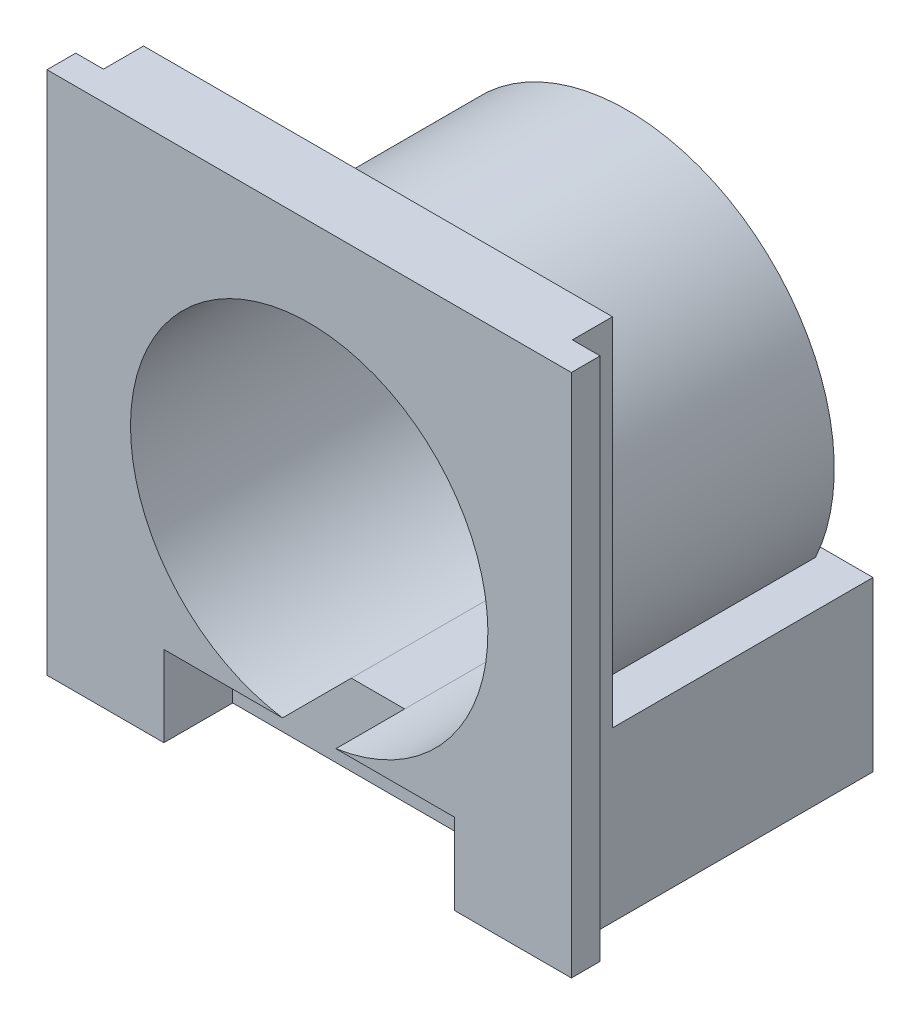
SolidWorks part; units mm, degrees
ref_plane "Front Plane" through (0, 0, 0) normal (0, 0, 1) x (1, 0, 0)
ref_plane "Top Plane" through (0, 0, 0) normal (0, 1, 0) x (1, 0, 0)
ref_plane "Right Plane" through (0, 0, 0) normal (1, 0, 0) x (0, 0, -1)
sketch "Sketch1" plane through (0, 0, 0) normal (0, 1, 0) x (1, 0, 0)
  line L0 (5.0691, -1.5049) -> (-12.7617, -1.505)
  line L1 (-12.7617, 8.401) -> (5.0691, 8.401)
  line L2 (-12.7617, 8.401) -> (-12.7617, -4.1212)
  line L3 (-12.7617, -4.1212) -> (5.0691, -4.1212)
  line L4 (5.0691, 8.401) -> (5.0691, -4.1212)
  line L5 (-13.8158, -3.029) -> (6.1232, -3.029)
  line L6 (-13.8158, -3.029) -> (-13.8158, -4.1212)
  line L7 (-13.8158, -4.1212) -> (6.1232, -4.1212)
  line L8 (6.1232, -3.029) -> (6.1232, -4.1212)
  line L9 (-9.3708, -4.1212) -> (1.6782, -4.1212)
  line L10 (-9.3708, -4.1212) -> (-9.3708, -1.0224)
  line L11 (-9.3708, -1.0224) -> (1.6782, -1.0224)
  line L12 (1.6782, -4.1212) -> (1.6782, -1.0224)
  line L14 (-12.7617, -3.0289) -> (5.0691, -3.0289)
  line L15 (-12.7617, -3.0289) -> (-12.7617, -1.505)
  line L16 (-12.7617, -1.505) -> (5.0691, -1.5049)
  line L17 (5.0691, -3.0289) -> (5.0691, -1.5049)
  point P12 (-3.8463, -1.0224)
  point P13 (-3.8463, -4.1212)
  point P14 (-3.8463, -3.029)
  point P17 (-12.7617, -3.0289)
  point P18 (5.0691, -3.0289)
  dimension "D1" = 17.8308
  dimension "D2" = 12.5222
  dimension "D3" = 0
  dimension "D4" = 3.0988
  dimension "D5" = 11.049
  dimension "D6" = 0
  dimension "D7" = 1.0922
  dimension "D8" = 19.939
  dimension "D9" = 0
  dimension "D10" = 1.524
extrude "Boss-Extrude1" add sketch "Sketch1" along normal blind 6.4008 contours L12 L5 L4 L1 L2 L10 L11 | L10 L9 L12 L11 region at (-3.8463, 0, -3.5947)
extrude "Boss-Extrude2" add sketch "Sketch1<3>" along normal blind 19.939 contours L6 L7 L2 L5 | L3 L10 L5 L2 | L7 L12 L5 L10 | L12 L3 L4 L5 | L8 L5 L4 L7 | L15 L14 L17 L16 region at (5.5962, 0, 3.5751) region at (3.3737, 0, 3.5751) region at (-3.8463, 0, 3.5751) region at (-11.0662, 0, 3.5751) region at (-13.2887, 0, 3.5751)
sketch "Sketch1<3>" plane through (0, 0, 0) normal (0, 1, 0) x (1, 0, 0) same geometry as "Sketch1"
extrude "Cut-Extrude1" cut sketch "Sketch1<4>" along normal blind 3.0734 contours L5 L12 L11 L10 | L7 L12 L5 L10 region at (-3.8463, 0, 2.267) region at (-3.8463, 0, 3.5751)
sketch "Sketch1<4>" plane through (0, 0, 0) normal (0, 1, 0) x (1, 0, 0) same geometry as "Sketch1"
sketch "Sketch2" plane through (0, 0, 1.5049) normal (0, 0, -1) x (-1, 0, 0)
  line L0 (12.7617, 19.939) -> (-5.0691, 19.939) construction
  circle A0 centre (3.8463, 9.6774) radius 7.874
  point P4 (3.8463, 19.939)
  dimension "D1" = 10.2616
  dimension "D2" = 0
extrude "Boss-Extrude3" add sketch "Sketch2" along normal blind 9.4742
sketch "Sketch3" plane through (0, 0, 4.1212) normal (0, 0, 1) x (1, 0, 0)
  line L0 (-3.8463, 19.939) -> (-3.8463, 9.7917)
  line L1 (-13.8158, 19.939) -> (6.1232, 19.939) construction
  circle A0 centre (-3.8463, 9.7917) radius 6.7945
  point P5 (-3.8463, 16.5862)
  line M3 (-9.3708, 3.0734) -> (1.6782, 3.0734)
  dimension "D1" = 3.3528
extrude "Cut-Extrude2" cut sketch "Sketch3" against normal blind 10.16 contours A0 M3 region at (1.1592, 5.4855, 4.1212)
